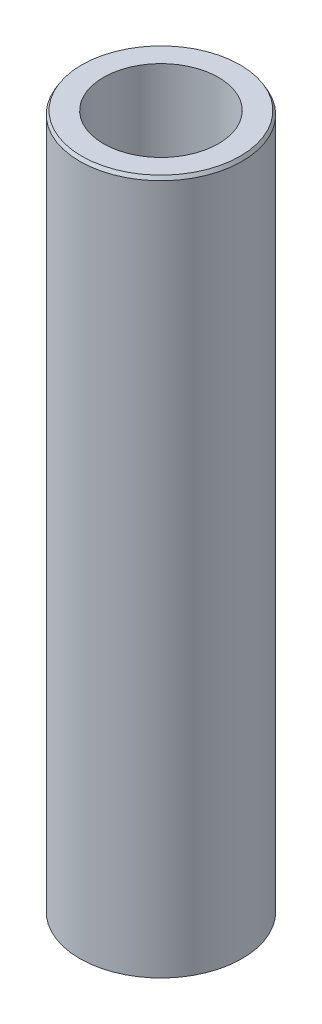
SolidWorks part; units mm, degrees
ref_plane "Front Plane" through (0, 0, 0) normal (0, 0, 1) x (1, 0, 0)
ref_plane "Top Plane" through (0, 0, 0) normal (0, 1, 0) x (1, 0, 0)
ref_plane "Right Plane" through (0, 0, 0) normal (1, 0, 0) x (0, 0, -1)
sketch "Sketch1" plane through (0, 0, 0) normal (0, 1, 0) x (1, 0, 0)
  circle A0 centre (0, 0) radius 27.5
  dimension "SHAFT_OD" = 55
extrude "Boss-Extrude1" add sketch "Sketch1" along normal blind 235.8024
sketch "Sketch2" plane through (0, 0, 0) normal (0, 1, 0) x (1, 0, 0)
  circle A0 centre (0, 0) radius 19.4873
  dimension "BORE_D" = 38.9745
extrude "Cut-Extrude1" cut sketch "Sketch2" along normal through all
chamfer "Chamfer1" distance 1.1656 angle 30 2 edges at (0, 235.8024, 27.5) (0, 0, 27.5) first distance on face at (0, 235.8024, 27.5) first distance on face at (0, 0, 19.4873)
